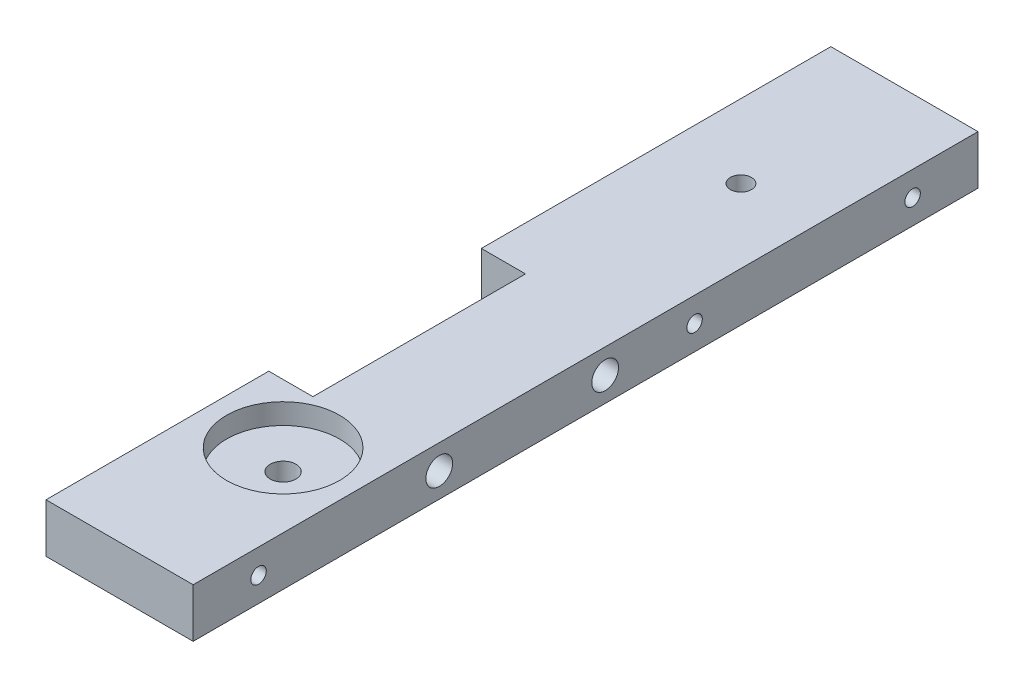
SolidWorks part; units mm, degrees
ref_plane "Front Plane" through (0, 0, 0) normal (0, 0, 1) x (1, 0, 0)
ref_plane "Top Plane" through (0, 0, 0) normal (0, 1, 0) x (1, 0, 0)
ref_plane "Right Plane" through (0, 0, 0) normal (1, 0, 0) x (0, 0, -1)
sketch "Sketch2" plane through (0, 0, 0) normal (0, 1, 0) x (1, 0, 0)
  line L0 (0, 0) -> (0, 152.4)
  line L1 (0, 152.4) -> (28.575, 152.4)
  line L2 (28.575, 152.4) -> (28.575, 0)
  line L3 (28.575, 0) -> (0, 0)
  dimension "D1" = 152.4
  dimension "D2" = 28.575
extrude "Boss-Extrude1" add sketch "Sketch2" along normal blind 9.525
sketch "Sketch3" plane through (0, 0, 0) normal (-1, 0, 0) x (0, 0, 1)
  line L3 (-152.4, 9.525) -> (0, 9.525) construction
  line L4 (-152.4, 9.525) -> (-152.4, 0) construction
  point P6 (-139.7, 4.7625)
  point P14 (-139.7, 4.7625)
  dimension "D1" = 4.7625
  dimension "D2" = 12.7
sketch "Sketch8" plane through (0, 0, 0) normal (-1, 0, 0) x (0, 0, 1)
  point P0 (-139.7, 4.7625)
hole_wizard "Ø3.0mm Dowel Hole1" positions "Sketch8" profile "Sketch9" hole size "Ø3.0" standard "ANSI Metric" end condition through all
sketch "Sketch9" plane through (0, 4.7625, -139.7) normal (0, 1, 0) x (0, 0, 1)
  line L0 (0, 0) -> (0, 28.575)
  line L1 (0, 28.575) -> (1.5, 28.575)
  line L2 (1.5, 28.575) -> (1.5, 0)
  line L5 (1.5, 0) -> (0, 0)
  line L11 (0, -6.35) -> (0, 107.95) construction
  dimension "Thru Hole Dia." = 3
  dimension "Thru Hole Depth" = 28.575
pattern_linear "LPattern1" count 4 spacing 42.3333 along (0, 0, 1) skipping (2, 0) of "Ø3.0mm Dowel Hole1"
sketch "Sketch12" plane through (0, 9.525, 0) normal (0, 1, 0) x (1, 0, 0)
  line L0 (28.575, 0) -> (28.575, 152.4) construction
  line L2 (0, 0) -> (28.575, 0) construction
  circle A1 centre (14.2875, 31.75) radius 10.975
  circle A2 centre (14.2875, 120.65) radius 2.05
  point P0 (14.2875, 120.65)
  point P1 (14.2875, 76.2)
  point P2 (14.2875, 31.75)
  dimension "D8" = 4.1
  dimension "D9" = 21.95
  dimension "D1" = 14.2875
  dimension "D2" = 14.2875
  dimension "D3" = 14.2875
  dimension "D4" = 76.2
  dimension "D5" = 44.45
  dimension "D6" = 44.45
sketch "Sketch13" plane through (0, 0, 0) normal (-1, 0, 0) x (0, 0, 1)
  line L2 (0, 9.525) -> (0, 0) construction
  line L3 (-152.4, 9.525) -> (0, 9.525) construction
  circle A0 centre (-80, 4.7625) radius 2.6
  circle A1 centre (-47.79, 4.7625) radius 2.6
  point P5 (-80, 4.7625)
  point P11 (-47.79, 4.7625)
  dimension "D1" = 80
  dimension "D2" = 4.7625
  dimension "D3" = 32.21
extrude "Cut-Extrude1" cut sketch "Sketch12" against normal through all contours A2
extrude "Cut-Extrude2" cut sketch "Sketch12<4>" against normal blind 4 contours A1
sketch "Sketch12<4>" plane through (0, 9.525, 0) normal (0, 1, 0) x (1, 0, 0) same geometry as "Sketch12"
sketch "Sketch15" plane through (0, 5.525, 0) normal (0, 1, 0) x (1, 0, 0)
  circle A0 centre (14.2875, 31.75) radius 2.5
  dimension "D1" = 5
extrude "Cut-Extrude3" cut sketch "Sketch15" against normal through all
extrude "Cut-Extrude4" cut sketch "Sketch13" against normal through all
sketch "Sketch17" plane through (0, 0, 0) normal (-1, 0, 0) x (0, 0, 1)
  line L0 (-152.4, 9.525) -> (0, 9.525) construction
  line L1 (-84.535, 9.525) -> (-43.255, 9.525)
  line L2 (-84.535, 9.525) -> (-84.535, 0)
  line L3 (-84.535, 0) -> (-43.255, 0)
  line L4 (-43.255, 9.525) -> (-43.255, 0)
  line L5 (-152.4, 0) -> (0, 0) construction
  circle A3 centre (-80, 4.7625) radius 2.6 construction
  circle A4 centre (-47.79, 4.7625) radius 2.6 construction
  point P12 (-84.535, 4.7625)
  dimension "D2" = 41.28
  dimension "D1" = 32.21
  dimension "D4" = 4.535
  dimension "D3" = 4.535
extrude "Cut-Extrude5" cut sketch "Sketch17" against normal offset from surface (8.575 mm away) 20 up to face at (28.575, 4.7625, -77.4)
